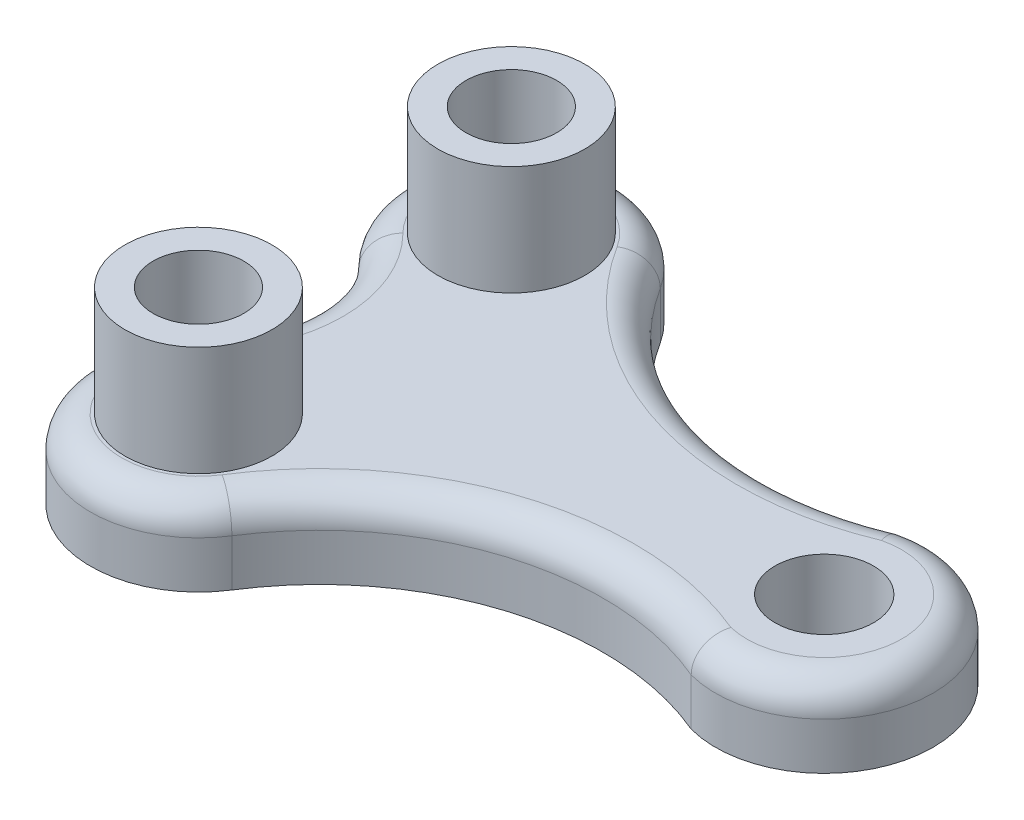
SolidWorks part; units mm, degrees
ref_plane "Alzado" through (0, 0, 0) normal (0, 0, 1) x (1, 0, 0)
ref_plane "Planta" through (0, 0, 0) normal (0, 1, 0) x (1, 0, 0)
ref_plane "Vista lateral" through (0, 0, 0) normal (1, 0, 0) x (0, 0, -1)
sketch "Croquis2" plane through (0, 0, 0) normal (0, 1, 0) x (1, 0, 0)
  line L0 (-5, 0) -> (15, 0) construction
  line L1 (7.5, 1.2807) -> (7.5, -1.2409) construction
  line L2 (0, 5) -> (15, 0) construction
  line L3 (15, 0) -> (0, -5) construction
  line L4 (7.5, 2.5) -> (9.1667, 7.5) construction
  line L5 (7.5, -2.5) -> (10.8333, -12.5) construction
  line L6 (9.1667, 7.5) -> (16.6667, 5) construction
  line L7 (9.1667, 7.5) -> (1.6667, 10) construction
  line L8 (0, 5) -> (3.6431, 15.9293) construction
  line L9 (15, 0) -> (16.6667, 5) construction
  circle A0 centre (0, 5) radius 1.45
  circle A1 centre (0, -5) radius 1.45
  circle A2 centre (15, 0) radius 1.475 construction
  arc A3 (14.1056, -3.3579) -> (14.1056, 3.3579) centre (15, 0) ccw
  arc A4 (2.9139, 6.847) -> (-2.4395, 2.5605) centre (0, 5) ccw
  arc A5 (2.9139, -6.847) -> (-2.4395, -2.5605) centre (0, -5) cw
  arc A6 (-2.4395, -2.5605) -> (-2.4395, 2.5605) centre (-5, 0) ccw
  arc A8 (2.9139, 6.847) -> (14.1056, 3.3579) centre (10.5657, 11.6971) ccw
  arc A9 (2.9139, -6.847) -> (14.1056, -3.3579) centre (10.5657, -11.6971) cw
  circle A11 centre (0, 5) radius 3.45 construction
  circle A12 centre (0, -5) radius 3.45 construction
  circle A13 centre (15, 0) radius 3.475 construction
  point P13 (3.45, -5)
  point P15 (18.3232, 1.016)
  point P32 (3.45, 5)
  dimension "D2" = 2.9
  dimension "D3" = 2.95
  dimension "D1" = 5
  dimension "D6" = 5
  dimension "D7" = 15
  dimension "D8" = 0
  dimension "D9" = 7.5
  dimension "D10" = 5
  dimension "D11" = 10
  dimension "D12" = 15
  dimension "D13" = 0
  dimension "D4" = 2
  dimension "D5" = 2
extrude "Saliente-Extruir1" add sketch "Croquis2" along normal blind 2.5
sketch "Croquis3" plane through (0, 2.5, 0) normal (0, 1, 0) x (1, 0, 0)
  circle A2 centre (0, 5) radius 2.45
  circle A3 centre (0, 5) radius 2.45
  circle A5 centre (0, -5) radius 2.45
  circle A6 centre (0, -5) radius 2.45
  dimension "D1" = 1
  dimension "D2" = 1
extrude "Cortar-Extruir1" cut sketch "Croquis3" against normal blind 1
fillet "Redondeo1" radius 1 6 edges at (7.8694, 2.5, -3.0483) (-2.1564, 2.5, -7.6931) (7.8694, 2.5, 3.0483) (18.475, 2.5, 0) (-2.1564, 2.5, 7.6931) (-1.3789, 2.5, 0)
sketch "Croquis7" plane through (0, 1.5, 0) normal (0, 1, 0) x (1, 0, 0)
  circle A0 centre (0, 5) radius 2.45
  circle A1 centre (0, -5) radius 2.45
  circle A2 centre (0, 5) radius 1.45
  circle A3 centre (0, -5) radius 1.45
  dimension "D1" = 4.9
extrude "Saliente-Extruir3" add sketch "Croquis7" along normal blind 4.5
sketch "Croquis8" plane through (0, 2.5, 0) normal (0, 1, 0) x (1, 0, 0)
  circle A0 centre (15, 0) radius 1.575
  dimension "D1" = 3.15
extrude "Cortar-Extruir3" cut sketch "Croquis8" against normal through all
sketch "Croquis9" plane through (0, 6, 0) normal (0, 1, 0) x (1, 0, 0)
  circle A0 centre (0, 5) radius 2.35
  circle A1 centre (0, -5) radius 2.35
  circle A2 centre (0, -5) radius 2.45
  circle A3 centre (0, 5) radius 2.45
  dimension "D1" = 4.9
  dimension "D2" = 4.9
  dimension "D3" = 0.1
  dimension "D4" = 0.1
extrude "Cortar-Extruir4" cut sketch "Croquis9" against normal blind 3.5
